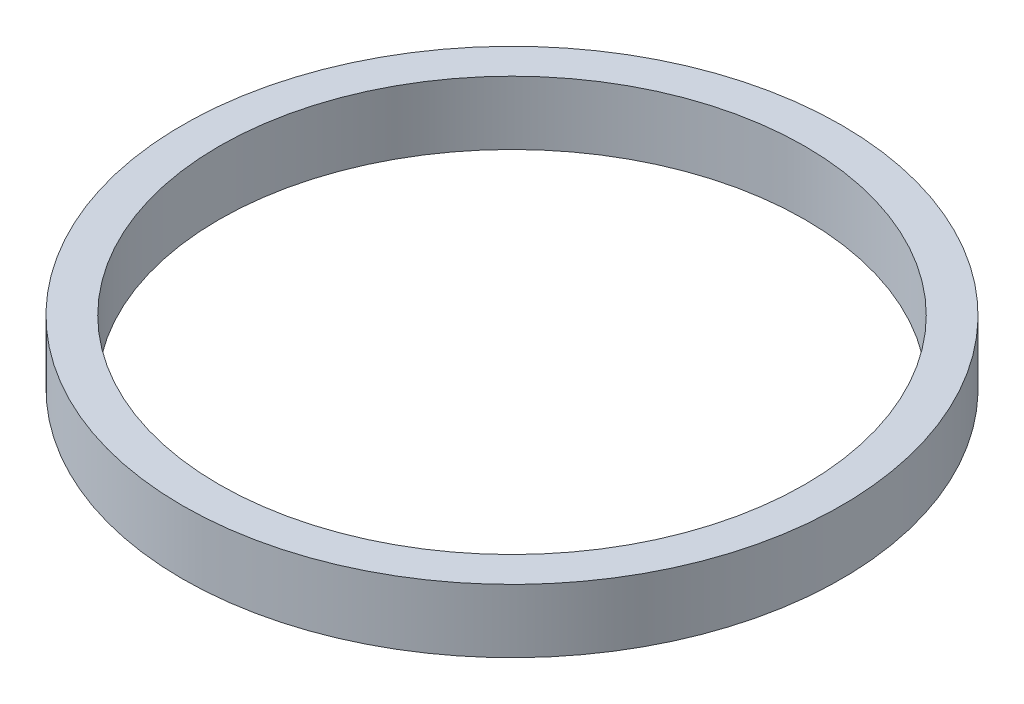
SolidWorks part; units mm, degrees
material "Rubber"
ref_plane "Front Plane" through (0, 0, 0) normal (0, 0, 1) x (1, 0, 0)
ref_plane "Top Plane" through (0, 0, 0) normal (0, 1, 0) x (1, 0, 0)
ref_plane "Right Plane" through (0, 0, 0) normal (1, 0, 0) x (0, 0, -1)
ref_axis "X-Axis" through (-88.99, 0, 0) along (1, 0, 0)
ref_axis "Y-Axis" through (0, 55, 0) along (0, -1, 0)
ref_axis "Z-Axis" through (0, 0, -88.99) along (0, 0, 1)
sketch "Sketch1" plane through (0, 0, 0) normal (0, 1, 0) x (1, 0, 0)
  circle A0 centre (0, 0) radius 6.75
  dimension "D1" = 13.5
extrude "Boss-Extrude1" add sketch "Sketch1" along normal mid plane 1.3
sketch "Sketch2" plane through (0, 0, 0) normal (0, 1, 0) x (1, 0, 0)
  circle A0 centre (0, 0) radius 6
  dimension "D1" = 12
extrude "Cut-Extrude1" cut sketch "Sketch2" against normal through all both and the other way through all
